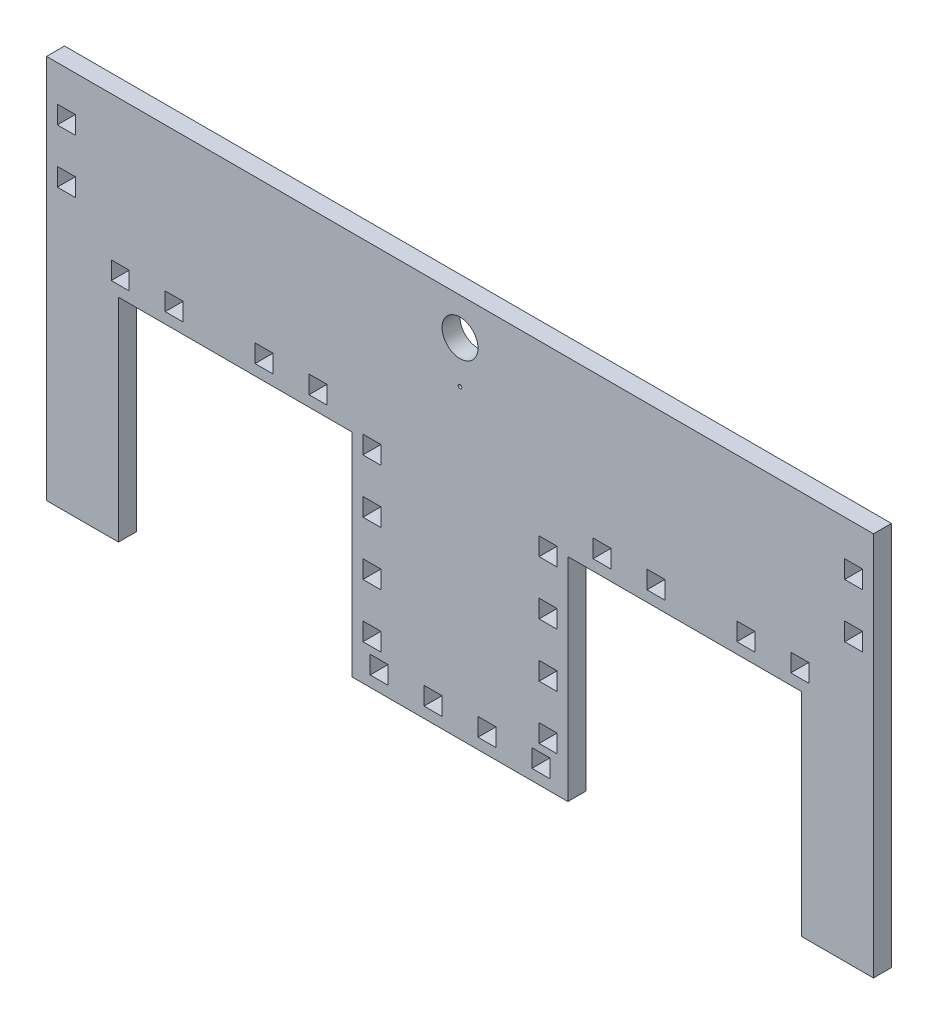
SolidWorks part; units mm, degrees
ref_plane "Plan de face" through (0, 0, 0) normal (0, 0, 1) x (1, 0, 0)
ref_plane "Plan de dessus" through (0, 0, 0) normal (0, 1, 0) x (1, 0, 0)
ref_plane "Plan de droite" through (0, 0, 0) normal (1, 0, 0) x (0, 0, -1)
sketch "Esquisse1" plane through (0, 0, 0) normal (0, 0, 1) x (1, 0, 0)
  line L0 (-115, 48) -> (115, 48)
  line L1 (115, 48) -> (115, 0)
  line L2 (115, 0) -> (30, 0) construction
  line L3 (30, 0) -> (30, -59)
  line L4 (30, -59) -> (-30, -59)
  line L5 (-30, -59) -> (-30, 0)
  line L6 (-30, 0) -> (-115, 0) construction
  line L7 (-115, 0) -> (-115, 48)
  line L8 (0, 48) -> (0, -59) construction
  line L10 (37, 8) -> (-37, 8) construction
  line L11 (-30, 0) -> (-95, 0)
  line L12 (-95, 0) -> (-95, -59)
  line L13 (-95, -59) -> (-115, -59)
  line L14 (-115, -59) -> (-115, 0)
  line L16 (115, -59) -> (115, 0)
  line L17 (95, -59) -> (115, -59)
  line L18 (95, 0) -> (95, -59)
  line L19 (30, 0) -> (95, 0)
  circle A0 centre (0, 37.7) radius 5
  circle A1 centre (0, 25.95) radius 0.5
  point P11 (0, -59)
  line B0 (107, 23) -> (107, 18)
  line B1 (107, 23) -> (112, 23)
  line B2 (112, 23) -> (112, 18)
  line B3 (107, 18) -> (112, 18)
  line B4 (107, 33) -> (107, 38)
  line B5 (107, 33) -> (112, 33)
  line B6 (112, 33) -> (112, 38)
  line B7 (107, 38) -> (112, 38)
  circle B8 centre (109.5, 28) radius 1.5 construction
  line B9 (22, -44) -> (22, -49)
  line B10 (22, -44) -> (27, -44)
  line B11 (27, -44) -> (27, -49)
  line B12 (22, -49) -> (27, -49)
  line B13 (22, -34) -> (22, -29)
  line B14 (22, -34) -> (27, -34)
  line B15 (27, -34) -> (27, -29)
  line B16 (22, -29) -> (27, -29)
  line B17 (24.5, -39) -> (18.2198, -39) construction
  circle B18 centre (24.5, -39) radius 1.5 construction
  line B19 (24.5, -14) -> (24.5, -4) construction
  line B20 (22, -14) -> (22, -19)
  line B21 (22, -14) -> (27, -14)
  line B22 (27, -14) -> (27, -19)
  line B23 (22, -19) -> (27, -19)
  line B24 (22, -4) -> (22, 1)
  line B25 (22, -4) -> (27, -4)
  line B26 (27, -4) -> (27, 1)
  line B27 (22, 1) -> (27, 1)
  line B28 (24.5, -9) -> (18.2198, -9) construction
  circle B29 centre (24.5, -9) radius 1.5 construction
  line B30 (22, -14) -> (27, -19) construction
  line B31 (82, 8) -> (77, 8)
  line B32 (82, 8) -> (82, 3)
  line B33 (82, 3) -> (77, 3)
  line B34 (77, 8) -> (77, 3)
  line B35 (92, 8) -> (97, 8)
  line B36 (92, 8) -> (92, 3)
  line B37 (92, 3) -> (97, 3)
  line B38 (97, 8) -> (97, 3)
  line B39 (87, 5.5) -> (87, 11.7802) construction
  circle B40 centre (87, 5.5) radius 1.5 construction
  line B41 (42, 8) -> (37, 8)
  line B42 (42, 8) -> (42, 3)
  line B43 (42, 3) -> (37, 3)
  line B44 (37, 8) -> (37, 3)
  line B45 (52, 8) -> (57, 8)
  line B46 (52, 8) -> (52, 3)
  line B47 (52, 3) -> (57, 3)
  line B48 (57, 8) -> (57, 3)
  line B49 (47, 5.5) -> (47, 11.7802) construction
  circle B50 centre (47, 5.5) radius 1.5 construction
  line B51 (-82, 8) -> (-77, 8)
  line B52 (-82, 8) -> (-82, 3)
  line B53 (-82, 3) -> (-77, 3)
  line B54 (-77, 8) -> (-77, 3)
  line B55 (-92, 8) -> (-97, 8)
  line B56 (-92, 8) -> (-92, 3)
  line B57 (-92, 3) -> (-97, 3)
  line B58 (-97, 8) -> (-97, 3)
  circle B59 centre (-87, 5.5) radius 1.5 construction
  line B60 (-22, -14) -> (-22, -19)
  line B61 (-22, -14) -> (-27, -14)
  line B62 (-27, -14) -> (-27, -19)
  line B63 (-22, -19) -> (-27, -19)
  line B64 (-22, -4) -> (-22, 1)
  line B65 (-22, -4) -> (-27, -4)
  line B66 (-27, -4) -> (-27, 1)
  line B67 (-22, 1) -> (-27, 1)
  circle B68 centre (-24.5, -9) radius 1.5 construction
  line B69 (-22, -44) -> (-22, -49)
  line B70 (-22, -44) -> (-27, -44)
  line B71 (-27, -44) -> (-27, -49)
  line B72 (-22, -49) -> (-27, -49)
  line B73 (-22, -34) -> (-22, -29)
  line B74 (-22, -34) -> (-27, -34)
  line B75 (-27, -34) -> (-27, -29)
  line B76 (-22, -29) -> (-27, -29)
  circle B77 centre (-24.5, -39) radius 1.5 construction
  line B78 (-42, 8) -> (-37, 8)
  line B79 (-42, 8) -> (-42, 3)
  line B80 (-42, 3) -> (-37, 3)
  line B81 (-37, 8) -> (-37, 3)
  line B82 (-52, 8) -> (-57, 8)
  line B83 (-52, 8) -> (-52, 3)
  line B84 (-52, 3) -> (-57, 3)
  line B85 (-57, 8) -> (-57, 3)
  circle B86 centre (-47, 5.5) radius 1.5 construction
  line B87 (-107, 23) -> (-107, 18)
  line B88 (-107, 23) -> (-112, 23)
  line B89 (-112, 23) -> (-112, 18)
  line B90 (-107, 18) -> (-112, 18)
  line B91 (-107, 33) -> (-107, 38)
  line B92 (-107, 33) -> (-112, 33)
  line B93 (-112, 33) -> (-112, 38)
  line B94 (-107, 38) -> (-112, 38)
  line B95 (-109.5, 28) -> (-103.2198, 28) construction
  circle B96 centre (-109.5, 28) radius 1.5 construction
  line B97 (-20, -51) -> (-25, -51)
  line B98 (-20, -51) -> (-20, -56)
  line B99 (-20, -56) -> (-25, -56)
  line B100 (-25, -51) -> (-25, -56)
  line B101 (-10, -51) -> (-5, -51)
  line B102 (-10, -51) -> (-10, -56)
  line B103 (-10, -56) -> (-5, -56)
  line B104 (-5, -51) -> (-5, -56)
  line B105 (-15, -53.5) -> (-15, -47.2198) construction
  circle B106 centre (-15, -53.5) radius 1.5 construction
  line B107 (20, -51) -> (25, -51)
  line B108 (20, -51) -> (20, -56)
  line B109 (20, -56) -> (25, -56)
  line B110 (25, -51) -> (25, -56)
  line B111 (10, -51) -> (5, -51)
  line B112 (10, -51) -> (10, -56)
  line B113 (10, -56) -> (5, -56)
  line B114 (5, -51) -> (5, -56)
  line B115 (15, -53.5) -> (15, -47.2198) construction
  circle B116 centre (15, -53.5) radius 1.5 construction
  dimension "D16" = 10
  dimension "D17" = 1
  dimension "D19" = 11.75
  dimension "D1" = 230
  dimension "D2" = 48
  dimension "D3" = 60
  dimension "D4" = 59
  dimension "D5" = 3
  dimension "D6" = 3
  dimension "D7" = 3
  dimension "D8" = 3
  dimension "D9" = 40
  dimension "D10" = 30
  dimension "D11" = 20
  dimension "D12" = 28
  dimension "D13" = 22.5
  dimension "D14" = 30
  dimension "D15" = 20
  dimension "D18" = 29.7
sketch_block_instance "Trou M3 plots 5mm-52"
sketch_block "Trou M3 plots 5mm" parameters "D2"=3, "D5"=3, "D1"=5, "D3"=5, "D4"=8
sketch_block_instance "Trou M3 plots 5mm-54"
sketch_block_instance "Trou M3 plots 5mm-55"
sketch_block_instance "Trou M3 plots 5mm-56"
sketch_block_instance "Trou M3 plots 5mm-58"
sketch_block_instance "Trou M3 plots 5mm-59"
sketch_block_instance "Trou M3 plots 5mm-60"
sketch_block_instance "Trou M3 plots 5mm-61"
sketch_block_instance "Trou M3 plots 5mm-62"
sketch_block_instance "Trou M3 plots 5mm-63"
sketch_block_instance "Trou M3 plots 5mm-64"
sketch_block_instance "Trou M3 plots 5mm-65"
extrude "Boss.-Extru.1" add sketch "Esquisse1" along normal blind 5
